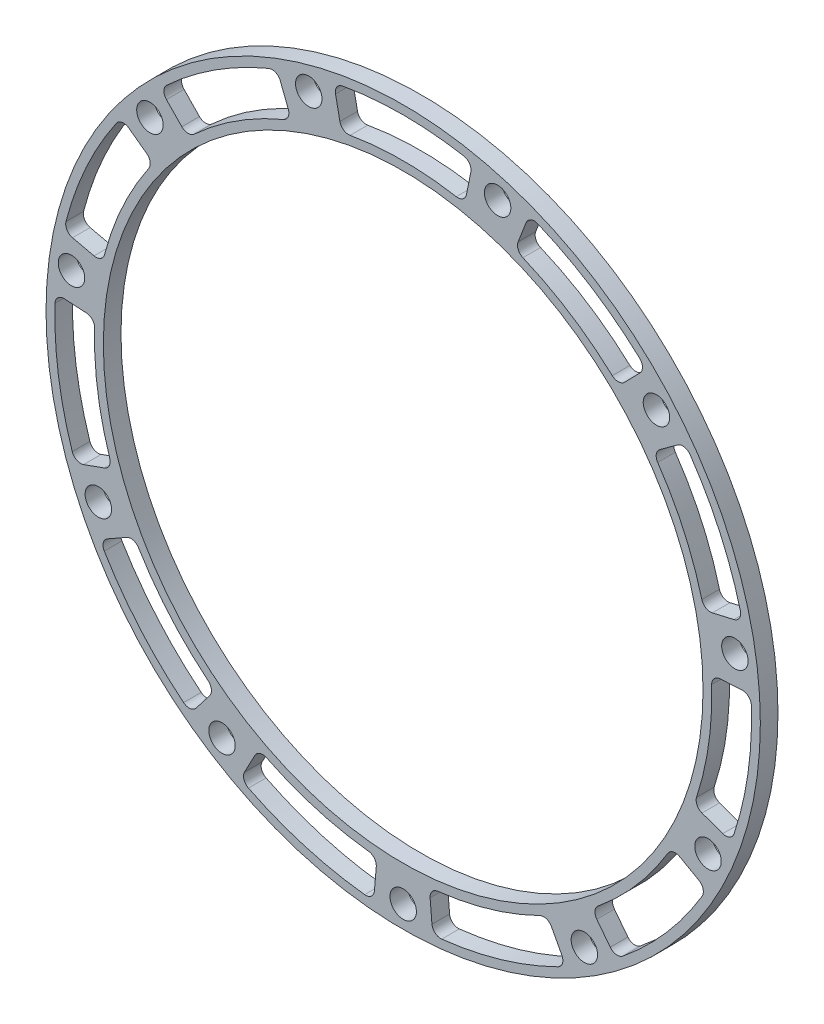
SolidWorks part; units mm, degrees
material "Thornel Mat VMA"
ref_plane "前视基准面" through (0, 0, 0) normal (0, 0, 1) x (1, 0, 0)
ref_plane "上视基准面" through (0, 0, 0) normal (0, 1, 0) x (1, 0, 0)
ref_plane "右视基准面" through (0, 0, 0) normal (1, 0, 0) x (0, 0, -1)
sketch "草图1" plane through (0, 0, 0) normal (0, 0, 1) x (1, 0, 0)
  circle A0 centre (0, 0) radius 34
  circle A1 centre (0, 0) radius 40.5
  circle A2 centre (0, -38) radius 1.5
  circle A3 centre (-20.5444, -31.9676) radius 1.5
  circle A4 centre (-34.566, -15.7858) radius 1.5
  circle A5 centre (-37.6132, 5.408) radius 1.5
  circle A6 centre (-28.7185, 24.8847) radius 1.5
  circle A7 centre (-10.7058, 36.4607) radius 1.5
  circle A8 centre (10.7058, 36.4607) radius 1.5
  circle A9 centre (28.7185, 24.8847) radius 1.5
  circle A10 centre (37.6132, 5.408) radius 1.5
  circle A11 centre (34.566, -15.7858) radius 1.5
  circle A12 centre (20.5444, -31.9676) radius 1.5
  point P28 (0, 0)
  dimension "D1" = 68
  dimension "D2" = 81
  dimension "D3" = 3
  dimension "D4" = 38
  dimension "D5" = 11
extrude "凸台-拉伸1" add sketch "草图1" along normal blind 2
sketch "草图2" plane through (0, 0, 2) normal (0, 0, 1) x (1, 0, 0)
  line L0 (-7.875, 38.707) -> (0, 0) construction
  line L1 (0, 0) -> (7.875, 38.707) construction
  line L2 (-7.875, 38.707) -> (-6.9779, 34.2974)
  line L3 (7.875, 38.707) -> (6.9779, 34.2974)
  line L4 (0, 39.5) -> (0, 0) construction
  arc A0 (-7.875, 38.707) -> (7.875, 38.707) centre (0, 0) cw
  arc A1 (-6.9779, 34.2974) -> (6.9779, 34.2974) centre (0, 0) cw
  dimension "D1" = 39.5
  dimension "D2" = 35
  dimension "D3" = 23
extrude "切除-拉伸1" cut sketch "草图2" against normal through all
fillet "圆角1" radius 1 4 edges at (7.875, 38.707, 1) (6.9779, 34.2974, 1) (-6.9779, 34.2974, 1) (-7.875, 38.707, 1)
ref_axis "基准轴1" through (0, 0, 2) along (0, 0, -1)
pattern_circular "阵列(圆周)1" count 11 over 360 about axis through (0, 0, 2) along (0, 0, -1) of "圆角1", "切除-拉伸1"
